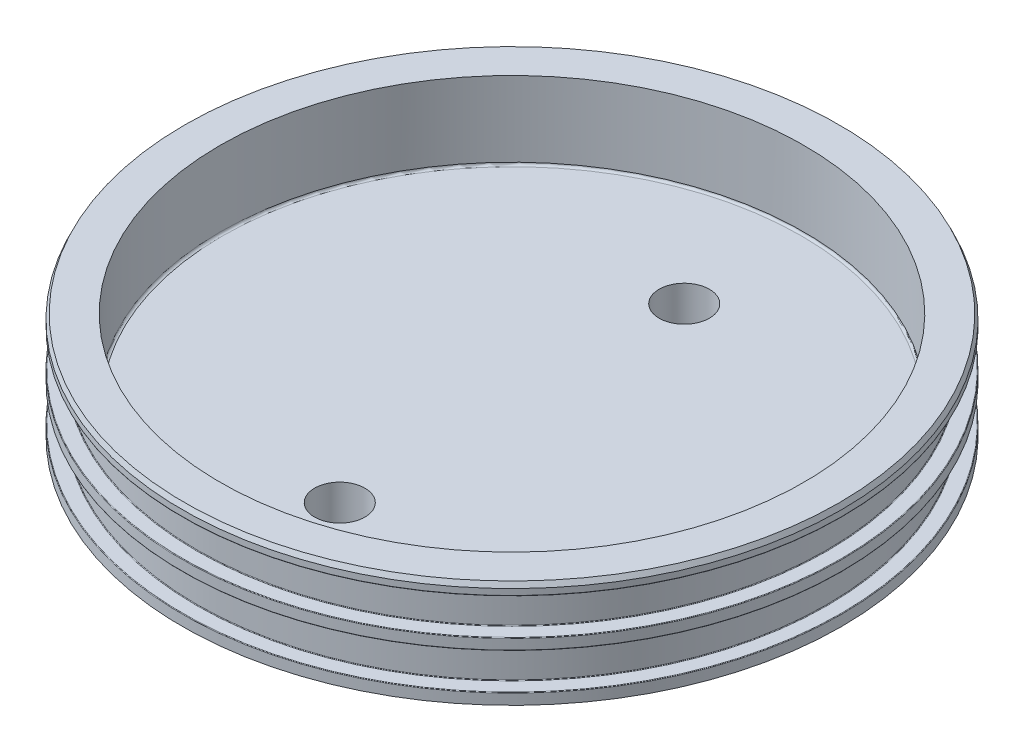
SolidWorks part; units mm, degrees
material "6061-T6 (SS)"
ref_plane "Front Plane" through (0, 0, 0) normal (0, 0, 1) x (1, 0, 0)
ref_plane "Top Plane" through (0, 0, 0) normal (0, 1, 0) x (1, 0, 0)
ref_plane "Right Plane" through (0, 0, 0) normal (1, 0, 0) x (0, 0, -1)
sketch "Sketch1" plane through (0, 0, 0) normal (0, 0, 1) x (1, 0, 0)
  line L0 (0, 48.1922) -> (0, -25.6743) construction
  line L1 (0, 0) -> (72.898, 0)
  line L2 (72.898, 0) -> (72.898, 2.4638)
  line L3 (72.898, 2.4638) -> (69.6468, 2.4638)
  line L4 (69.6468, 2.4638) -> (69.6468, 10.4648)
  line L5 (69.6468, 10.4648) -> (72.898, 10.4648)
  line L6 (72.898, 10.4648) -> (72.898, 12.9286)
  line L7 (72.898, 12.9286) -> (69.6468, 12.9286)
  line L8 (64.5668, 23.4696) -> (64.5668, 6.35)
  line L9 (64.5668, 6.35) -> (0, 6.35)
  line L10 (0, 6.35) -> (0, 0)
  line L11 (69.6468, 12.9286) -> (69.6468, 20.9296)
  line L12 (69.6468, 20.9296) -> (72.898, 20.9296)
  line L13 (72.898, 20.9296) -> (72.898, 23.4696)
  line L14 (72.898, 23.4696) -> (64.5668, 23.4696)
  dimension "D1" = 145.796
  dimension "D2" = 8.001
  dimension "D5" = 6.35
  dimension "D7" = 8.001
  dimension "D4" = 2.4638
  dimension "D8" = 2.54
  dimension "D3" = 69.6468
  dimension "D6" = 5.08
revolve "Revolve1" add sketch "Sketch1" angle 360 about L0
sketch "Sketch6" plane through (0, 0, 0) normal (0, -1, 0) x (1, 0, 0)
  circle A0 centre (0, 0) radius 66.04
  dimension "D1" = 132.08
extrude "Boss-Extrude1" add sketch "Sketch6" along normal blind 2.54
hole_wizard "Pipe Tap Drill for 1/4 Tap - GN2" positions "Sketch2" profile "Sketch3" hole size "1/4" standard "ANSI Inch" end condition through all
sketch "Sketch2" plane through (0, 6.35, 0) normal (0, 1, 0) x (1, 0, 0)
  point P4 (0, -38.1)
  dimension "D1" = 38.1
sketch "Sketch3" plane through (0, 6.35, 38.1) normal (1, 0, 0) x (0, 0, 1)
  line L0 (0, 0) -> (0, 8.89)
  line L1 (0, 8.89) -> (5.5626, 8.89)
  line L2 (5.5626, 8.89) -> (5.5626, 0)
  line L5 (5.5626, 0) -> (0, 0)
  line L11 (0, -6.35) -> (0, 107.95) construction
  dimension "Thru Hole Dia." = 11.1252
  dimension "Thru Hole Depth" = 8.89
fillet "CNC ID Fillet" radius 0.127 5 edges at (-69.6468, 10.4648, 0) (-69.6468, 2.4638, 0) (-69.6468, 20.9296, 0) (-69.6468, 12.9286, 0) (66.04, 0, 0)
fillet "CNC OD Fillet" radius 0.127 5 edges at (-72.898, 10.4648, 0) (-72.898, 2.4638, 0) (66.04, -2.54, 0) (-72.898, 20.9296, 0) (-72.898, 12.9286, 0)
chamfer "CNC Chamfers" distance 0.508 angle 65 1 edges at (-72.898, 23.4696, 0) first distance on face at (-64.5668, 23.4696, 0)
fillet "CNC Bore Fillet" radius 0.508 1 edges at (-64.5668, 6.35, 0)
hole_wizard "Pipe Tap Drill for 1/4 Tap - Relief Valve" positions "Sketch13" profile "Sketch14" hole size "1/4" standard "ANSI Inch" end condition through all
sketch "Sketch13" plane through (0, -2.54, 0) normal (0, -1, 0) x (-1, 0, 0)
  point P4 (0, 38.1)
  dimension "D1" = 38.1
sketch "Sketch14" plane through (0, -2.54, -38.1) normal (1, 0, 0) x (0, 0, -1)
  line L0 (0, 0) -> (0, 26.0096)
  line L1 (0, 26.0096) -> (5.5626, 26.0096)
  line L2 (5.5626, 26.0096) -> (5.5626, 0)
  line L5 (5.5626, 0) -> (0, 0)
  line L11 (0, -6.35) -> (0, 107.95) construction
  dimension "Thru Hole Dia." = 11.1252
  dimension "Thru Hole Depth" = 26.0096
equation "\"D3@Sketch1\"=5.484/2"
